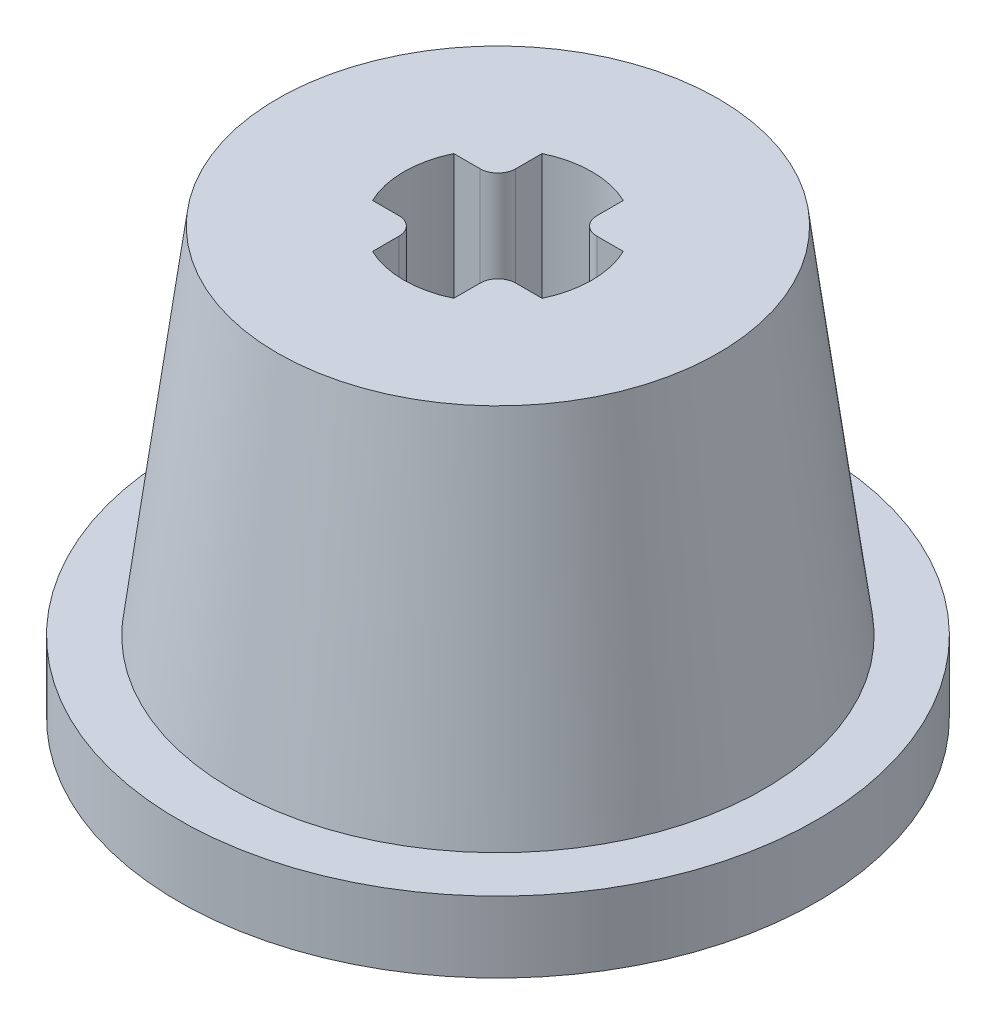
SolidWorks part; units mm, degrees
ref_plane "Front Plane" through (0, 0, 0) normal (0, 0, 1) x (1, 0, 0)
ref_plane "Top Plane" through (0, 0, 0) normal (0, 1, 0) x (1, 0, 0)
ref_plane "Right Plane" through (0, 0, 0) normal (1, 0, 0) x (0, 0, -1)
sketch "Sketch1" plane through (0, 0, 0) normal (0, 1, 0) x (1, 0, 0)
  circle A0 centre (0, 0) radius 7.5
  dimension "D1" = 15
extrude "Boss-Extrude1" add sketch "Sketch1" along normal blind 10
sketch "Sketch2" plane through (0, 0, 0) normal (1, 0, 0) x (0, 0, -1)
  line L0 (-7.5, 0) -> (-6.2136, 10)
  line L1 (7.5, 10) -> (-7.5, 10) construction
  line L2 (-6.2136, 10) -> (-7.5, 10)
  line L3 (-7.5, 10) -> (-7.5, 0)
  line L4 (0, 0) -> (0, 50000) construction
  line L5 (-7.5, 0) -> (7.5, 0) construction
  point P11 (0, 0)
  dimension "D1" = 7.33
revolve "Cut-Revolve1" cut sketch "Sketch2" angle 360 about L4
sketch "Sketch3" plane through (0, 0, 0) normal (0, -1, 0) x (-1, 0, 0)
  circle A0 centre (0, 0) radius 9
  dimension "D1" = 18
extrude "Boss-Extrude2" add sketch "Sketch3" along normal blind 2
sketch "Sketch4" plane through (0, -2, 0) normal (0, -1, 0) x (1, 0, 0)
  line L0 (1.145, -2.3899) -> (1.145, 2.3899)
  line L1 (-1.145, -2.3899) -> (-1.145, 2.3899)
  line L2 (0, 0) -> (35355.3391, 35355.3391) construction
  line L3 (0.8543, 0) -> (50000.8543, 0) construction
  line L4 (-2.3899, 1.145) -> (2.3899, 1.145)
  line L5 (-2.3899, -1.145) -> (2.3899, -1.145)
  circle A0 centre (0, 0) radius 2.65
  dimension "D1" = 5.3
  dimension "D2" = 2.29
  dimension "D3" = 45
extrude "Cut-Extrude1" cut sketch "Sketch4" against normal through all contours L1 L5 L0 L4 | L4 A0 L5 L1 | L0 A0 L1 L4 | L5 A0 L4 L0 | L1 A0 L0 L5 region at (0, -2, -1.8571) region at (0, -2, 0) region at (1.8571, -2, 0) region at (0, -2, 1.8571) region at (-1.8571, -2, 0)
fillet "Fillet1" radius 0.5 4 edges at (1.145, 4, 1.145) (1.145, 4, -1.145) (-1.145, 4, -1.145) (-1.145, 4, 1.145)
